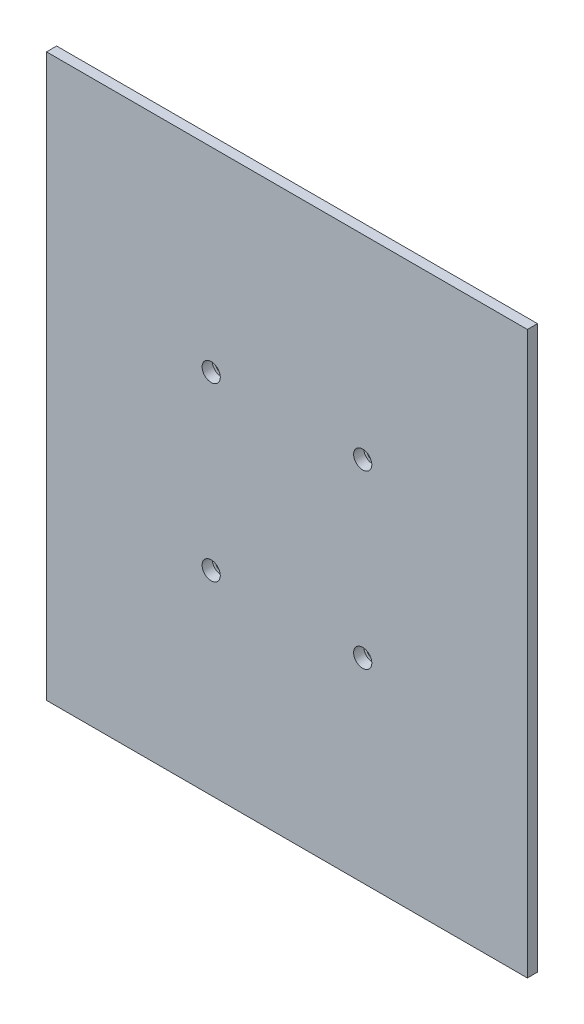
SolidWorks part; units mm, degrees
ref_plane "前视基准面" through (0, 0, 0) normal (0, 0, 1) x (1, 0, 0)
ref_plane "上视基准面" through (0, 0, 0) normal (0, 1, 0) x (1, 0, 0)
ref_plane "右视基准面" through (0, 0, 0) normal (1, 0, 0) x (0, 0, -1)
sketch "草图1" plane through (0, 0, 0) normal (0, 0, 1) x (1, 0, 0)
  line L0 (0, 0) -> (0, -105)
  line L1 (0, -105) -> (95, -105)
  line L2 (95, -105) -> (95, 0)
  line L3 (95, 0) -> (0, 0)
extrude "凸台-拉伸3" add sketch "草图1" along normal blind 10 contours L2 L3 L0 L1
sketch "草图10" plane through (0, 0, 0) normal (0, 0, -1) x (-1, 0, 0)
  circle A0 centre (-85, -10) radius 4.5
  circle A1 centre (-85, -95) radius 4.5
  circle A2 centre (-10, -95) radius 4.5
  circle A3 centre (-10, -10) radius 4.5
extrude "切除-拉伸4" cut sketch "草图10" against normal blind 5
sketch "草图12" plane through (0, 0, 10) normal (0, 0, 1) x (1, 0, 0)
  line L2 (47.5, 81.5) -> (161.5, 81.5)
  line L3 (161.5, 81.5) -> (161.5, -186.5)
  line L4 (161.5, -186.5) -> (-66.5, -186.5)
  line L5 (-66.5, -186.5) -> (-66.5, 81.5)
  line L6 (-66.5, 81.5) -> (47.5, 81.5)
extrude "凸台-拉伸4" add sketch "草图12" against normal blind 5
sketch "草图13" plane through (0, 0, 10) normal (0, 0, 1) x (1, 0, 0)
  line L0 (-71.5, 86.5) -> (-71.5, -191.5)
  line L1 (-71.5, -191.5) -> (166.5, -191.5)
  line L3 (-66.5, 81.5) -> (161.5, 81.5)
  line L4 (-66.5, 81.5) -> (-66.5, -186.5)
  line L5 (-71.5, 86.5) -> (166.5, 86.5)
  line L8 (166.5, 86.5) -> (166.5, -191.5)
  line L9 (-66.5, -186.5) -> (161.5, -186.5)
  line L10 (161.5, 81.5) -> (161.5, -186.5)
extrude "凸台-拉伸5" add sketch "草图13" along normal blind 30 separate body
sketch "草图14" plane through (0, 0, 5) normal (0, 0, -1) x (-1, 0, 0)
  line L1 (-166.5, 86.5) -> (71.5, 86.5)
  line L2 (-166.5, 86.5) -> (-166.5, -191.5)
  line L3 (-166.5, -191.5) -> (71.5, -191.5)
  line L4 (71.5, 86.5) -> (71.5, -191.5)
  line L5 (-161.5, 81.5) -> (66.5, 81.5)
  line L6 (-161.5, 81.5) -> (-161.5, -186.5)
  line L7 (-161.5, -186.5) -> (66.5, -186.5)
  line L8 (66.5, 81.5) -> (66.5, -186.5)
extrude "凸台-拉伸6" add sketch "草图14" against normal blind 5
sketch "草图17" plane through (0, 0, 40) normal (0, 0, 1) x (1, 0, 0)
  line L1 (-200.175, 200.4143) -> (264.6919, 200.4143)
  line L2 (-200.175, 200.4143) -> (-200.175, -276.8364)
  line L3 (-200.175, -276.8364) -> (264.6919, -276.8364)
  line L4 (264.6919, 200.4143) -> (264.6919, -276.8364)
extrude "切除-拉伸5" cut sketch "草图17" against normal blind 30
extrude "切除-拉伸6" cut sketch "草图10<2>" against normal blind 10
sketch "草图10<2>" plane through (0, 0, 0) normal (0, 0, -1) x (-1, 0, 0) same geometry as "草图10"
sketch "草图19" plane through (0, 0, 0) normal (0, 0, -1) x (-1, 0, 0)
  circle A0 centre (-85, -10) radius 4.5
  circle A1 centre (-85, -10) radius 3
  circle A2 centre (-10, -10) radius 4.5
  circle A3 centre (-10, -10) radius 3
  circle A4 centre (-85, -95) radius 3
  circle A5 centre (-85, -95) radius 4.5
  circle A6 centre (-10, -95) radius 4.5
  circle A7 centre (-10, -95) radius 3
extrude "凸台-拉伸7" add sketch "草图19" against normal blind 5
